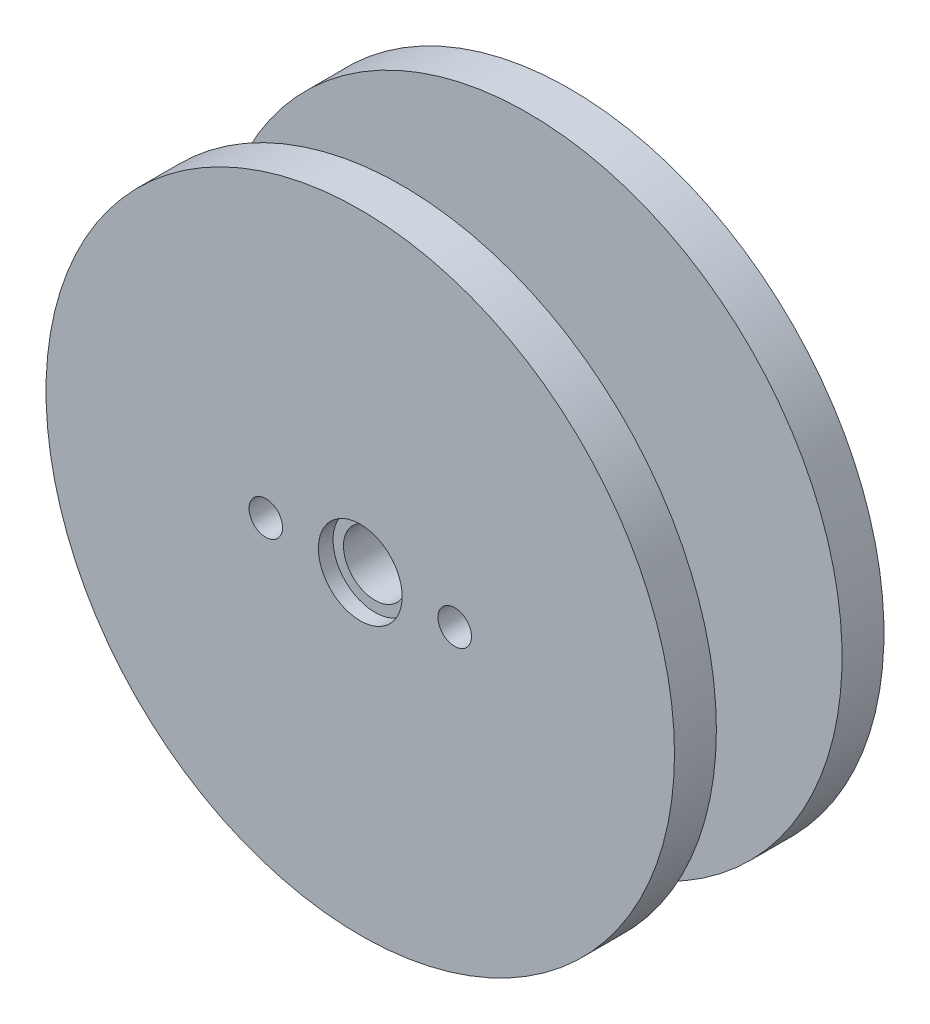
SolidWorks part; units mm, degrees
ref_plane "Front Plane" through (0, 0, 0) normal (0, 0, 1) x (1, 0, 0)
ref_plane "Top Plane" through (0, 0, 0) normal (0, 1, 0) x (1, 0, 0)
ref_plane "Right Plane" through (0, 0, 0) normal (1, 0, 0) x (0, 0, -1)
sketch "Sketch1" plane through (0, 0, 0) normal (0, 0, 1) x (1, 0, 0)
  circle A0 centre (0, 0) radius 2.5
  dimension "D1" = 5
extrude "Boss-Extrude1" add sketch "Sketch1" along normal blind 6 contours A0
sketch "Sketch2" plane through (0, 0, 0) normal (0, 0, -1) x (-1, 0, 0)
  circle A0 centre (0, 0) radius 15
  dimension "D1" = 30
extrude "Boss-Extrude2" add sketch "Sketch2" along normal blind 2
sketch "Sketch3" plane through (0, 0, 6) normal (0, 0, 1) x (1, 0, 0)
  circle A0 centre (0, 0) radius 15
  dimension "D1" = 30
extrude "Boss-Extrude3" add sketch "Sketch3" along normal blind 2 contours A0
fillet "Fillet9" radius 3 1 edges at (2.5, 0, 0) type face fillet first side face at (2.5, 0, 0) second side face at (2.5, 0, 6)
fillet "Fillet10" radius 3 1 edges at (2.5, 0, 6) type face fillet first side face at (2.5, 0, 6) second side face at (-2.5, 0, 3)
sketch "Sketch4" plane through (0, 0, -2) normal (0, 0, -1) x (-1, 0, 0)
  circle A0 centre (0, 0) radius 1.5
  dimension "D1" = 3
extrude "Cut-Extrude1" cut sketch "Sketch4" against normal blind 10
sketch "Sketch5" plane through (0, 0, 8) normal (0, 0, 1) x (1, 0, 0)
  circle A0 centre (0, 0) radius 1.9994
  dimension "D1" = 3.9987
extrude "Cut-Extrude2" cut sketch "Sketch5" against normal blind 0.7
sketch "Sketch7" plane through (0, 0, 8) normal (0, 0, 1) x (1, 0, 0)
  line L0 (1.9994, 0) -> (4.5094, 0)
  line L1 (-1.9994, 0) -> (-4.5094, 0)
  circle A0 centre (0, 0) radius 1.9994 construction
  circle A1 centre (0, 0) radius 1.9994 construction
  circle A2 centre (4.5094, 0) radius 0.8
  circle A3 centre (-4.5094, 0) radius 0.8
  dimension "D1" = 4.5094
  dimension "1.6" = 1.6
  dimension "D2" = 1.6
  dimension "D3" = 4.5094
extrude "Cut-Extrude6" cut sketch "Sketch7" against normal blind 3 contours A2 | A3
